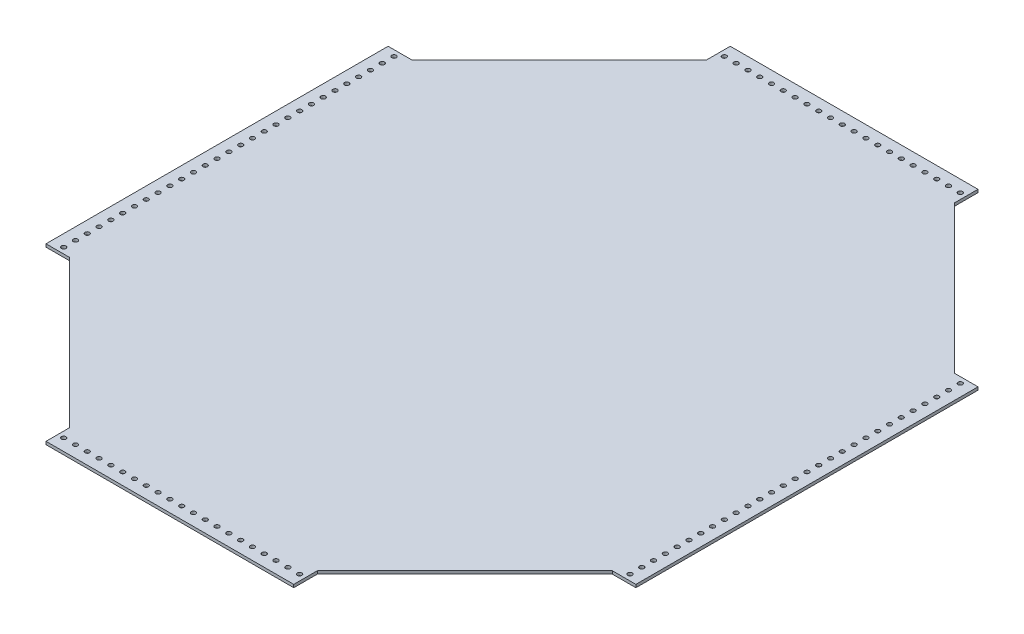
SolidWorks part; units mm, degrees
material "ABS PC"
ref_plane "Front Plane" through (0, 0, 0) normal (0, 0, 1) x (1, 0, 0)
ref_plane "Top Plane" through (0, 0, 0) normal (0, 1, 0) x (1, 0, 0)
ref_plane "Right Plane" through (0, 0, 0) normal (1, 0, 0) x (0, 0, -1)
sketch "Sketch1" plane through (0, 0, 0) normal (0, 1, 0) x (1, 0, 0)
  line L1 (-317.5, -368.3) -> (317.5, -368.3)
  line L2 (-317.5, -368.3) -> (-317.5, 368.3)
  line L3 (-317.5, 368.3) -> (317.5, 368.3)
  line L4 (317.5, -368.3) -> (317.5, 368.3)
  line L5 (-317.5, -368.3) -> (317.5, 368.3) construction
  line L6 (-317.5, 368.3) -> (317.5, -368.3) construction
  point P0 (0, 0)
  dimension "D1" = 635
  dimension "D2" = 736.6
extrude "Base" add sketch "Sketch1" along normal blind 3.175
sketch "Sketch3" plane through (0, 3.175, 0) normal (0, 1, 0) x (1, 0, 0)
  line L0 (317.5, -368.3) -> (317.5, 368.3) construction
  line L6 (317.5, 368.3) -> (-317.5, 368.3) construction
  line L7 (-317.5, 368.3) -> (-317.5, -368.3) construction
  circle A0 centre (-304.8, 355.6) radius 2.413
  circle A1 centre (304.8, 355.6) radius 2.413
  dimension "D1" = 4.826
  dimension "D2" = 4.826
  dimension "D3" = 12.7
  dimension "D4" = 12.7
  dimension "D5" = 12.7
  dimension "D6" = 12.7
extrude "Initial Pattern Hole" cut sketch "Sketch3" against normal through all
pattern_linear "Hole Pattern 1" count 58 spacing 12.7 along (0, 0, 1) of "Initial Pattern Hole"
pattern_linear "Hole Pattern 2" count 48 spacing 12.7 along (1, 0, 0) of face at (-304.8, 0, 358.013) of face at (-304.8, 0, -353.187)
sketch "Sketch2" plane through (0, 0, 0) normal (0, -1, 0) x (-1, 0, 0)
  line L16 (-317.5, 368.3) -> (-317.5, 184.15)
  line L17 (-317.5, -368.3) -> (-317.5, 368.3) construction
  line L18 (-317.5, 184.15) -> (-292.1004, 184.15)
  line L19 (-292.1004, 184.15) -> (-133.35, 342.9004)
  line L20 (-133.35, 342.9004) -> (-133.35, 368.3)
  line L21 (-317.5, 368.3) -> (317.5, 368.3) construction
  line L22 (-133.35, 368.3) -> (-317.5, 368.3)
  line L23 (133.35, 368.3) -> (317.5, 368.3)
  line L24 (317.5, 368.3) -> (317.5, 184.15)
  line L25 (317.5, 368.3) -> (317.5, -368.3) construction
  line L26 (317.5, 184.15) -> (292.1004, 184.15)
  line L27 (292.1004, 184.15) -> (133.35, 342.9004)
  line L28 (133.35, 342.9004) -> (133.35, 368.3)
  line L29 (317.5, -368.3) -> (317.5, -184.15)
  line L30 (317.5, -184.15) -> (292.1004, -184.15)
  line L31 (292.1004, -184.15) -> (133.35, -342.9004)
  line L32 (133.35, -342.9004) -> (133.35, -368.3)
  line L33 (317.5, -368.3) -> (307.213, -368.3) construction
  line L34 (133.35, -368.3) -> (317.5, -368.3)
  line L35 (-133.35, -368.3) -> (-133.35, -342.9004)
  line L36 (-133.35, -342.9004) -> (-292.1004, -184.15)
  line L37 (-292.1004, -184.15) -> (-317.5, -184.15)
  line L38 (-317.5, -184.15) -> (-317.5, -368.3)
  line L39 (-317.5, -368.3) -> (-133.35, -368.3)
  dimension "D1" = 184.15
extrude "Module Cutout" cut sketch "Sketch2" against normal through all
sketch "Sketch4" [suppressed] plane through (0, 3.175, 0) normal (0, 1, 0) x (1, 0, 0)
  line L0 (-317.5, 368.3) -> (-317.5, 158.75)
  line L1 (-317.5, 368.3) -> (-317.5, -368.3) construction
  line L2 (-317.5, 158.75) -> (-253.3187, 158.75)
  line L3 (-253.3187, 158.75) -> (-107.95, 304.1187)
  line L4 (-107.95, 304.1187) -> (-107.95, 368.3)
  line L5 (317.5, 368.3) -> (-317.5, 368.3) construction
  line L6 (-107.95, 368.3) -> (-317.5, 368.3)
  line L7 (317.5, 368.3) -> (107.95, 368.3)
  line L8 (107.95, 368.3) -> (107.95, 304.1187)
  line L9 (107.95, 304.1187) -> (253.3187, 158.75)
  line L10 (253.3187, 158.75) -> (317.5, 158.75)
  line L11 (317.5, -368.3) -> (317.5, 368.3) construction
  line L12 (317.5, 158.75) -> (317.5, 368.3)
  line L13 (317.5, -368.3) -> (317.5, -158.75)
  line L14 (317.5, -158.75) -> (253.3187, -158.75)
  line L15 (253.3187, -158.75) -> (107.95, -304.1187)
  line L16 (107.95, -304.1187) -> (107.95, -368.3)
  line L17 (-302.387, -368.3) -> (302.387, -368.3) construction
  line L18 (107.95, -368.3) -> (317.5, -368.3)
  line L19 (-317.5, -368.3) -> (-107.95, -368.3)
  line L20 (-107.95, -368.3) -> (-107.95, -304.1187)
  line L21 (-107.95, -304.1187) -> (-253.3187, -158.75)
  line L22 (-253.3187, -158.75) -> (-317.5, -158.75)
  line L23 (-317.5, -158.75) -> (-317.5, -368.3)
  dimension "D1" = 209.55
extrude "Top Module Cutout" [suppressed] cut sketch "Sketch4" against normal through all
